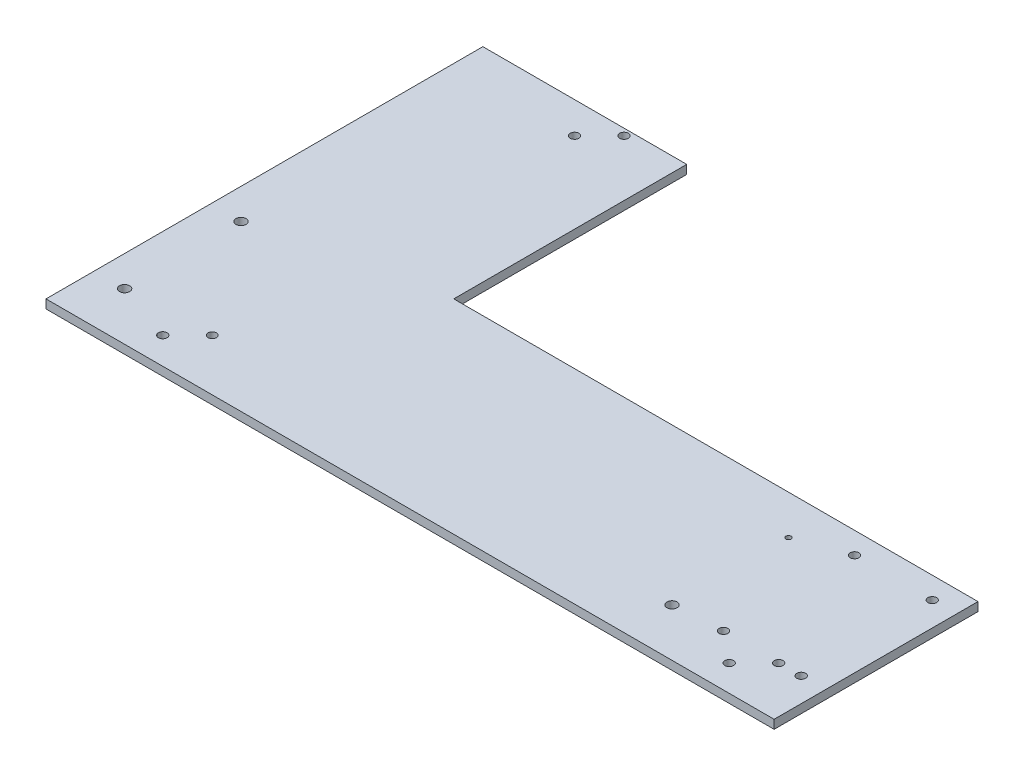
SolidWorks part; units mm, degrees
ref_plane "Front Plane" through (0, 0, 0) normal (0, 0, 1) x (1, 0, 0)
ref_plane "Top Plane" through (0, 0, 0) normal (0, 1, 0) x (1, 0, 0)
ref_plane "Right Plane" through (0, 0, 0) normal (1, 0, 0) x (0, 0, -1)
sketch "Sketch1" plane through (0, 0, 0) normal (0, 1, 0) x (1, 0, 0)
  line L0 (-125, -35) -> (125, -35)
  line L2 (-125, -35) -> (-125, 35)
  line L4 (125, -35) -> (125, 35)
  line L5 (-125, -35) -> (125, 35) construction
  line L6 (-125, 35) -> (125, -35) construction
  line L15 (-55, 35) -> (125, 35)
  line L17 (-125, 35) -> (-125, 115)
  line L18 (-125, 115) -> (-55, 115)
  line L19 (-55, 35) -> (-55, 115)
  circle A0 centre (-94.1332, -25.7565) radius 1.5
  circle A1 centre (-85.6479, -17.2712) radius 1.4446
  circle A2 centre (100.5732, -25.9922) radius 1.5
  circle A3 centre (109.0585, -17.5069) radius 1.5
  circle A4 centre (-82.7607, 104.2435) radius 1.5
  circle A5 centre (-74.2754, 112.7288) radius 1.5
  circle A6 centre (-114.5451, 21.4861) radius 1.75
  circle A7 centre (-114.5451, -18.4693) radius 1.7515
  circle A8 centre (73.4549, 21.4861) radius 0.8847
  circle A9 centre (73.4549, -18.5139) radius 1.75
  circle A10 centre (90.0422, 27.5719) radius 1.5
  circle A11 centre (116.7221, 27.5719) radius 1.5
  circle A12 centre (116.7221, -17.4281) radius 1.5
  circle A13 centre (90.0422, -17.4281) radius 1.5
  point P0 (0, 0)
  dimension "D1" = 250
  dimension "D2" = 70
  dimension "D3" = 70
  dimension "D4" = 150
extrude "Boss-Extrude1" add sketch "Sketch1" along normal blind 3
